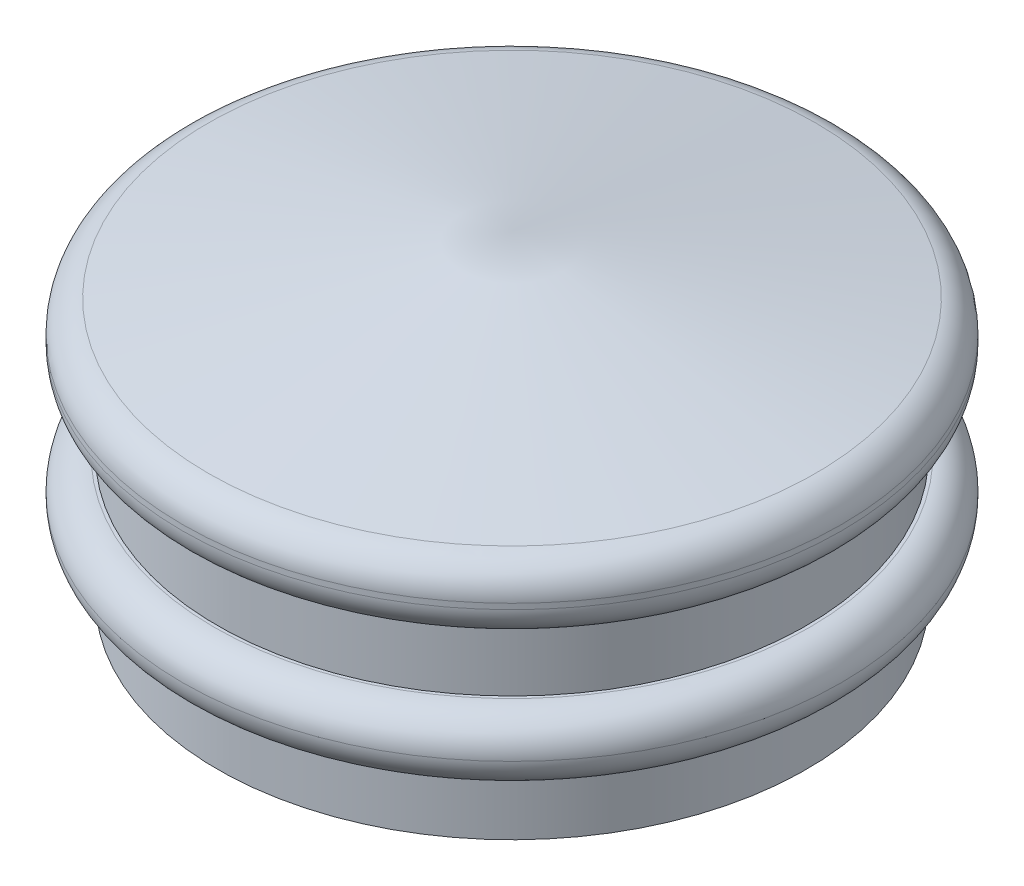
SolidWorks part; units mm, degrees
ref_plane "Front" through (0, 0, 0) normal (0, 0, 1) x (1, 0, 0)
ref_plane "Top" through (0, 0, 0) normal (0, 1, 0) x (1, 0, 0)
ref_plane "Right" through (0, 0, 0) normal (1, 0, 0) x (0, 0, -1)
sketch "Sketch1" plane through (0, 0, 0) normal (0, 0, 1) x (1, 0, 0)
  line L1 (0, 7.5) -> (-7.75, 6.0182)
  line L2 (-7.75, 6.0182) -> (-7.75, 4.5182)
  line L3 (-7.75, 4.5182) -> (-6.9274, 4.5182)
  line L4 (-6.9274, 4.5182) -> (-6.9274, 2.9278)
  line L5 (-6.9274, 2.9278) -> (-7.75, 2.9278)
  line L6 (-7.75, 2.9278) -> (-7.75, 1.4278)
  line L8 (-7.75, 1.4278) -> (-6.9274, 1.4278)
  line L9 (-6.9274, 1.4278) -> (-6.9274, 0)
  line L10 (-6.9274, 0) -> (-5.1363, 0)
  line L11 (-5.1363, 0) -> (-3.1267, 1.4278)
  line L12 (-3.1267, 1.4278) -> (-3.1267, 4.7)
  line L13 (-3.1267, 4.7) -> (0, 4.7)
  line L14 (0, 0) -> (0, 4.7) construction
  line L15 (0, 4.7) -> (0, 7.5)
  dimension "D1" = 1.5
  dimension "D2" = 7.5
  dimension "D3" = 4.7
  dimension "D4" = 7.75
revolve "Revolve1" add sketch "Sketch1" angle 360 about L14
fillet "Fillet1" radius 0.75 4 edges at (0, 6.0182, -7.75) (0, 4.5182, -7.75) (0, 2.9278, -7.75) (0, 1.4278, -7.75)
